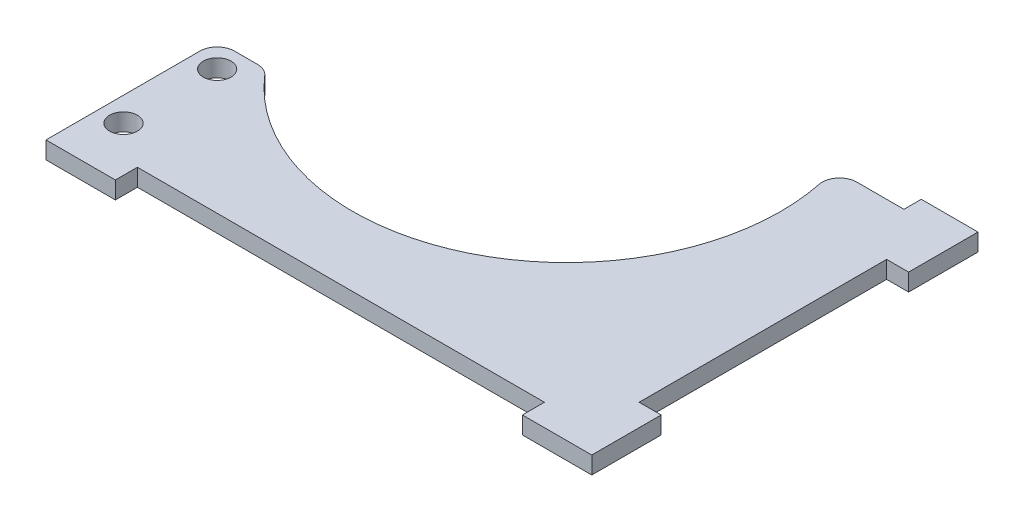
SolidWorks part; units mm, degrees
ref_plane "Front Plane" through (0, 0, 0) normal (0, 0, 1) x (1, 0, 0)
ref_plane "Top Plane" through (0, 0, 0) normal (0, 1, 0) x (1, 0, 0)
ref_plane "Right Plane" through (0, 0, 0) normal (1, 0, 0) x (0, 0, -1)
sketch "Sketch1" plane through (0, 0, 0) normal (0, 1, 0) x (1, 0, 0)
  line L0 (-78.675, -55.675) -> (-58.675, -55.675)
  line L1 (-58.675, -55.675) -> (-58.675, -49.325)
  line L2 (-58.675, -49.325) -> (58.675, -49.325)
  line L3 (58.675, -49.325) -> (58.675, -55.675)
  line L4 (58.675, -55.675) -> (78.675, -55.675)
  line L5 (78.675, -55.675) -> (78.675, -35.675)
  line L6 (78.675, -35.675) -> (72.325, -35.675)
  line L7 (72.325, -35.675) -> (72.325, 35.675)
  line L8 (72.325, 35.675) -> (78.675, 35.675)
  line L9 (78.675, 35.675) -> (78.675, 55.675)
  line L10 (78.675, 55.675) -> (62.325, 55.675)
  line L11 (62.325, 55.675) -> (62.325, 50.675)
  line L12 (62.325, 50.675) -> (42.325, 50.675)
  line L13 (-78.675, -55.675) -> (-78.675, -6.325)
  line L14 (-78.675, -6.325) -> (-64.675, -6.325)
  arc A0 (-64.675, -6.325) -> (42.325, 50.675) centre (-16.6151, 32.3871) ccw
  circle A1 centre (-71.675, -40.325) radius 4
  circle A2 centre (-71.675, -13.325) radius 4
  point P21 (-71.675, -9.325)
  point P22 (-71.675, -6.325)
  point P23 (-71.675, -44.325)
  point P24 (-67.675, -40.325)
  point P25 (-75.675, -13.325)
  point P26 (0, -49.325)
  point P28 (72.325, 0)
  point P30 (-16.6151, -29.325)
  dimension "D2" = 8
  dimension "D1" = 20
  dimension "D3" = 5
  dimension "D4" = 6.35
  dimension "D5" = 40
  dimension "D6" = 3
  dimension "D7" = 3
  dimension "D8" = 140
  dimension "D9" = 100
  dimension "D10" = 20
  dimension "D11" = 10
  dimension "D12" = 20
  dimension "D13" = 5
extrude "Boss-Extrude1" add sketch "Sketch1" along normal mid plane 5
fillet "Fillet1" radius 5 3 edges at (42.325, 0, -50.675) (-78.675, 0, 6.325) (-64.675, 0, 6.325)
